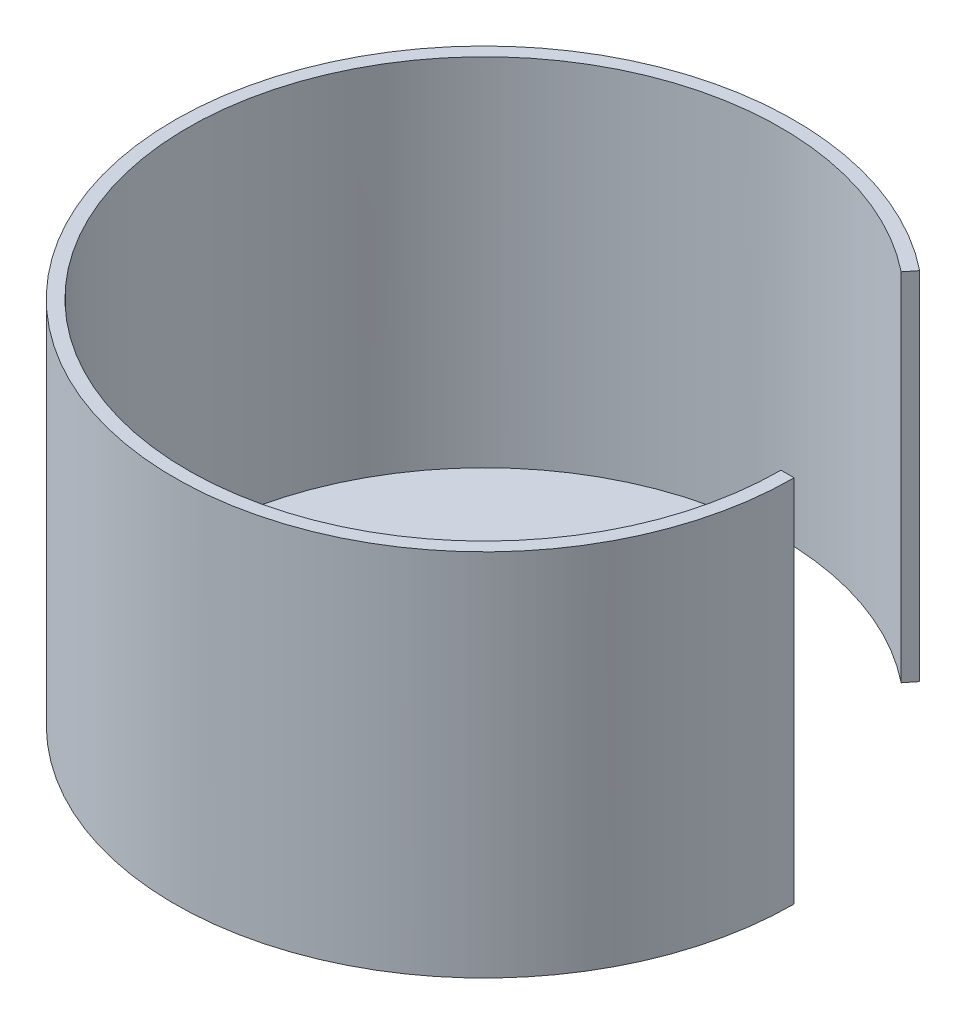
SolidWorks part; units mm, degrees
ref_plane "Front Plane" through (0, 0, 0) normal (0, 0, 1) x (1, 0, 0)
ref_plane "Top Plane" through (0, 0, 0) normal (0, 1, 0) x (1, 0, 0)
ref_plane "Right Plane" through (0, 0, 0) normal (1, 0, 0) x (0, 0, -1)
sketch "Sketch1" plane through (0, 0, 0) normal (0, 1, 0) x (1, 0, 0)
  line L0 (-3.3378, 14.6239) -> (-10.4585, 45.8216)
  line L1 (15, 0) -> (47, 0)
  line L2 (-52.4413, 0) -> (78.3185, 0) construction
  arc A0 (-10.4585, 45.8216) -> (47, 0) centre (0, 0) ccw
  arc A1 (15, 0) -> (-3.3378, 14.6239) centre (0, 0) ccw
  dimension "D1" = 94
  dimension "D3" = 30
  dimension "D2" = 102.857
extrude "Boss-Extrude1" add sketch "Sketch1" along normal blind 2
sketch "Sketch2" plane through (0, 2, 0) normal (0, 1, 0) x (1, 0, 0)
  line L0 (28.057, 35.1824) -> (29.304, 36.7461)
  line L1 (45, 0) -> (47, 0)
  arc A0 (29.304, 36.7461) -> (47, 0) centre (0, 0) ccw
  arc A1 (-10.4585, 45.8216) -> (47, 0) centre (0, 0) ccw construction
  arc A2 (28.057, 35.1824) -> (45, 0) centre (0, 0) ccw
  dimension "D1" = 2
  dimension "D2" = 51.429
extrude "Boss-Extrude2" add sketch "Sketch2" along normal blind 54
chamfer "Chamfer1" distance 2 angle 82 1 edges at (30, 2, 0) first distance on face at (35.6667, 19.3333, 0)
